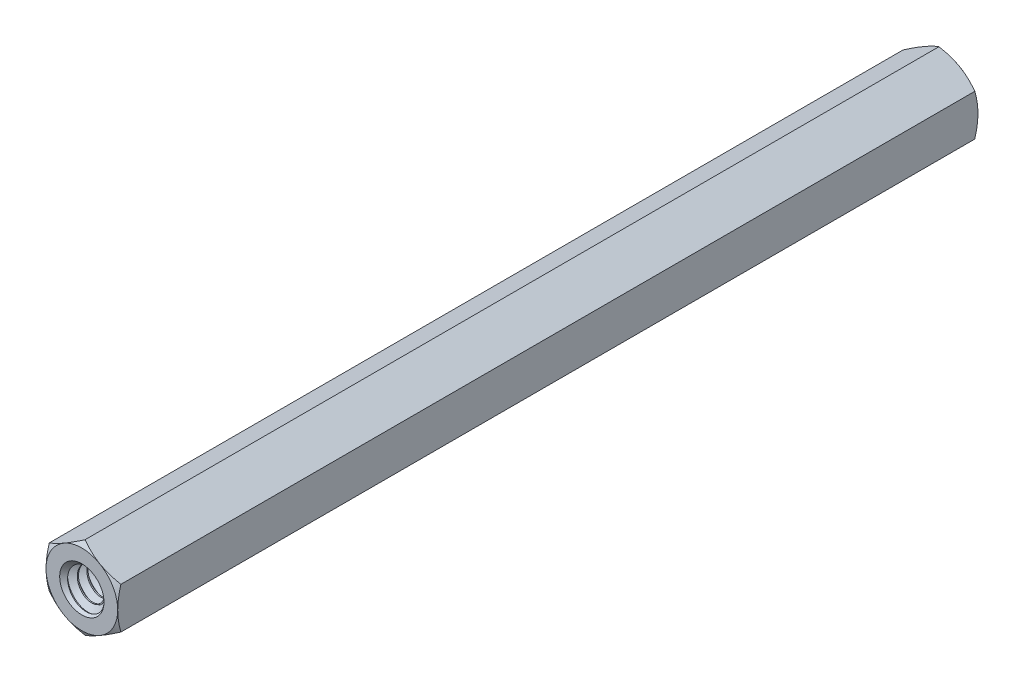
SolidWorks part; units mm, degrees
ref_plane "Front Plane" through (0, 0, 0) normal (0, 0, 1) x (1, 0, 0)
ref_plane "Top Plane" through (0, 0, 0) normal (0, 1, 0) x (1, 0, 0)
ref_plane "Right Plane" through (0, 0, 0) normal (1, 0, 0) x (0, 0, -1)
sketch "Sketch3" plane through (0, 0, 0) normal (1, 0, 0) x (0, 0, -1)
  line L0 (-28.575, 0) -> (28.575, 0) construction
  line L1 (0, 2.3813) -> (0, -2.3813) construction
  line L2 (-28.575, 1.4224) -> (-28.575, -1.4224) construction
  point P2 (22.225, 0)
  point P3 (-22.225, 0)
  dimension "Length" = 57.15
  dimension "Min Thread Length" = 6.35
  dimension "D1" = 6.35
  dimension "Thread Dia" = 2.8448
  dimension "Hex" = 4.7625
sketch "Sketch1" plane through (0, 0, 0) normal (0, 0, 1) x (1, 0, 0)
  line L1 (0, 2.7496) -> (-2.3812, 1.3748)
  line L2 (-2.3812, 1.3748) -> (-2.3812, -1.3748)
  line L3 (-2.3812, -1.3748) -> (0, -2.7496)
  line L4 (0, -2.7496) -> (2.3813, -1.3748)
  line L5 (2.3813, -1.3748) -> (2.3813, 1.3748)
  line L6 (2.3813, 1.3748) -> (0, 2.7496)
  circle A0 centre (0, 0) radius 2.3813 construction
  circle A1 centre (0, 0) radius 1.4224
extrude "Extrude1" add sketch "Sketch1" along normal up to vertex (28.575 mm away) and the other way up to vertex (28.575 mm away) up to point (0, 0, 28.575) other way up to point (0, 0, -28.575)
sketch "Sketch11" plane through (0, 0, -28.575) normal (0, 0, -1) x (-1, 0, 0)
  circle A0 centre (0, 0) radius 1.4224 construction
  circle A1 centre (0, 0) radius 1.4224
curve "Helix/Spiral1" pitch 0.635 height 57.785 radius 1.4224 centre (0, 0, -28.575) axis (0, 0, 1) start towards (0, 1, 0) parameters "Pitch"=0.635
sketch "Sketch12" plane through (0, 0, 0) normal (1, 0, 0) x (0, 0, -1)
  line L0 (29.1306, 1.4224) -> (28.575, 1.4224)
  line L1 (29.1306, 1.4224) -> (28.8925, 1.01)
  line L2 (28.8925, 1.01) -> (28.8131, 1.01)
  line L3 (28.8131, 1.01) -> (28.575, 1.4224)
  line L4 (28.8528, 1.01) -> (28.8528, 1.4224) construction
  line L5 (29.0116, 1.2162) -> (28.6941, 1.2162) construction
  dimension "D1" = 0.0794
  dimension "D2" = 0.3175
  dimension "D3" = 60
sweep "Sweep1" add profiles "Sketch12" path "Helix/Spiral1"
sketch "Sketch6" plane through (0, 0, -28.575) normal (0, 0, -1) x (-1, 0, 0)
  line L6 (0, 2.7496) -> (-2.3813, 1.3748)
  line L7 (-2.3813, 1.3748) -> (-2.3813, -1.3748)
  line L8 (-2.3813, -1.3748) -> (0, -2.7496)
  line L9 (0, -2.7496) -> (2.3812, -1.3748)
  line L10 (2.3812, -1.3748) -> (2.3812, 1.3748)
  line L11 (2.3812, 1.3748) -> (0, 2.7496)
  line L12 (0, 2.7496) -> (-2.3813, 1.3748)
  line L13 (-2.3813, 1.3748) -> (-2.3813, -1.3748)
  line L14 (-2.3813, -1.3748) -> (0, -2.7496)
  line L15 (0, -2.7496) -> (2.3812, -1.3748)
  line L16 (2.3812, -1.3748) -> (2.3812, 1.3748)
  line L17 (2.3812, 1.3748) -> (0, 2.7496)
  dimension "D1" = 0
extrude "Extrude2" cut sketch "Sketch6" along normal through all
sketch "Sketch7" plane through (0, 0, -28.575) normal (0, 0, -1) x (-1, 0, 0)
  circle A2 centre (0, 0) radius 1.4732
  circle A3 centre (0, 0) radius 1.4732
  dimension "D1" = 0.0508
extrude "Extrude3" cut sketch "Sketch7" against normal through all draft 43
sketch "Sketch8" plane through (0, 0, -28.575) normal (0, 0, -1) x (-1, 0, 0)
  circle A0 centre (0, 0) radius 2.3813 construction
  circle A1 centre (0, 0) radius 2.3813
extrude "Extrude4" cut sketch "Sketch8" against normal through all draft 60 flip side to cut
mirror "Mirror1" about plane through (0, 0, 0) normal (0, 0, 1) of "Extrude2", "Extrude3", "Extrude4"
sketch "Sketch9" plane through (0, 0, 0) normal (1, 0, 0) x (0, 0, -1)
  line L1 (-22.225, 1.4732) -> (22.225, 1.4732)
  line L2 (-22.225, 1.4732) -> (-22.225, 0)
  line L3 (-22.225, 0) -> (22.225, 0)
  line L4 (22.225, 1.4732) -> (22.225, 0)
  line L7 (-28.575, 0) -> (28.575, 0) construction
revolve "Revolve" add sketch "Sketch9" angle 360 about L0
sketch "Sketch10" plane through (0, 0, 0) normal (1, 0, 0) x (0, 0, -1)
  line L0 (28.575, 1.4224) -> (22.225, 1.4224)
  line L1 (-28.575, 1.4224) -> (-22.225, 1.4224)
  line L2 (22.225, 1.4224) -> (22.225, -1.4224)
  line L3 (-28.575, -1.4732) -> (-22.225, -1.4732)
  line L4 (-22.225, 1.4224) -> (-22.225, -1.4732)
  line L5 (22.225, -1.4224) -> (28.575, -1.4224)
sketch "Sketch13" plane through (0, 0, 28.575) normal (0, 0, 1) x (1, 0, 0)
  line L0 (0, 0) -> (1.01, 0) construction
  line L1 (0, 0) -> (0.7141, 0.7141) construction
  line L2 (0, 0) -> (0.7141, -0.7141) construction
  arc A0 (0.5533, -0.8449) -> (0.9908, -0.1958) centre (0, 0) ccw construction
  arc A1 (-0.7076, -0.7206) -> (0, -1.01) centre (0, 0) ccw construction
  dimension "D1" = 45
  dimension "D2" = 45
equation "\"D1@Sketch3\" = \"Min Thread Length@Sketch3\""
equation "\"D3@Helix/Spiral1\" = \"Length@Sketch3\"+\"Pitch@Helix/Spiral1\""
equation "\"D1@Sketch12\" = \"Pitch@Helix/Spiral1\"*.125"
equation "\"D2@Sketch12\" = \"Pitch@Helix/Spiral1\"*.5"
